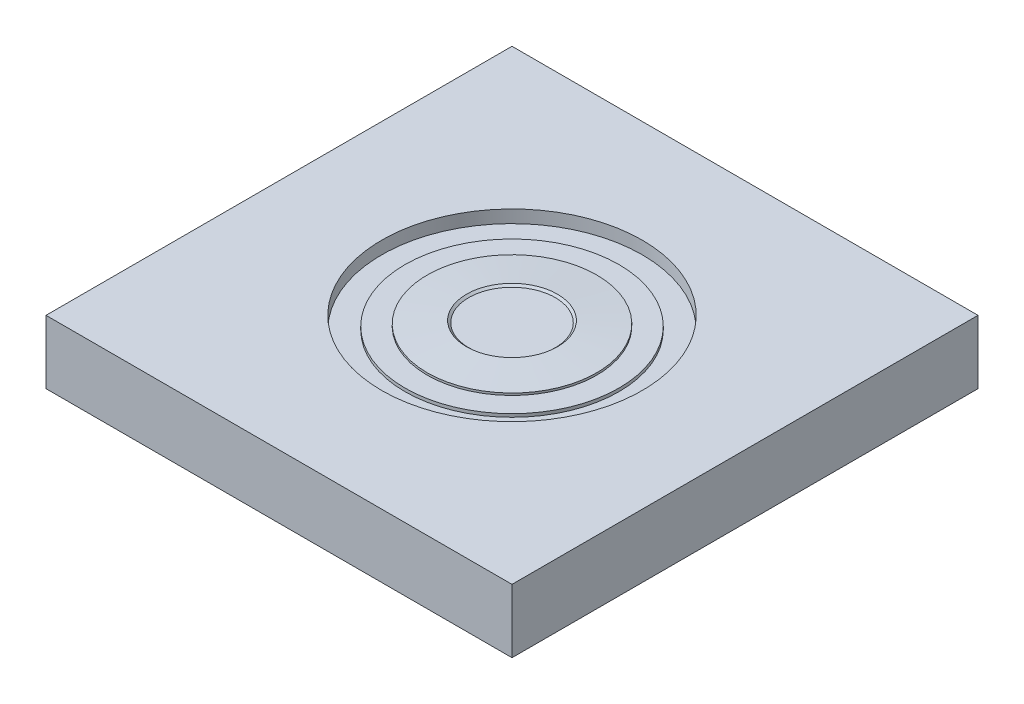
SolidWorks part; units mm, degrees
ref_plane "Front Plane" through (0, 0, 0) normal (0, 0, 1) x (1, 0, 0)
ref_plane "Top Plane" through (0, 0, 0) normal (0, 1, 0) x (1, 0, 0)
ref_plane "Right Plane" through (0, 0, 0) normal (1, 0, 0) x (0, 0, -1)
sketch "Sketch1" plane through (0, 0, 0) normal (0, 1, 0) x (1, 0, 0)
  line L0 (0, 0) -> (0, 237921.0776) construction
  line L1 (0, 0) -> (-237921.0776, 0) construction
  line L3 (110, -110) -> (-110, -110)
  line L4 (110, -110) -> (110, 110)
  line L5 (110, 110) -> (-110, 110)
  line L6 (-110, -110) -> (-110, 110)
  line L7 (110, -110) -> (-110, 110) construction
  line L8 (110, 110) -> (-110, -110) construction
  point P5 (0, 0)
  dimension "D1" = 220
  dimension "D2" = 220
extrude "Boss-Extrude1" add sketch "Sketch1" along normal blind 30
sketch "Sketch2" plane through (0, 30, 0) normal (0, 1, 0) x (1, 0, 0)
  line L0 (0, 0) -> (0, 50000) construction
  line L1 (0, 0) -> (-50000, 0) construction
  circle A0 centre (0, 0) radius 61.5
  circle A1 centre (0, 0) radius 50.5
  dimension "D1" = 123
  dimension "D2" = 101
extrude "Cut-Extrude1" cut sketch "Sketch2" against normal blind 6
sketch "Sketch3" plane through (0, 30, 0) normal (0, 1, 0) x (1, 0, 0)
  circle A0 centre (0, 0) radius 50.5
  circle A1 centre (0, 0) radius 40
  dimension "D1" = 101
  dimension "D2" = 80
extrude "Cut-Extrude2" cut sketch "Sketch3" against normal blind 4.5
sketch "Sketch4" plane through (0, 30, 0) normal (0, 1, 0) x (1, 0, 0)
  circle A0 centre (0, 0) radius 40
  dimension "D1" = 80
extrude "Cut-Extrude3" cut sketch "Sketch4" against normal blind 3.5
sketch "Sketch5" plane through (0, 26.5, 0) normal (0, 1, 0) x (1, 0, 0)
  circle A0 centre (0, 0) radius 40
  dimension "D1" = 80
ref_plane "Plane1" through (0, 28, 0) normal (0, 1, 0) x (1, 0, 0)
sketch "Sketch6" plane through (0, 28, 0) normal (0, 1, 0) x (1, 0, 0)
  circle A0 centre (0, 0) radius 20
  dimension "D1" = 40
loft "Loft1" add profiles "Sketch5", "Sketch6" connector at (7.742, 26.5, 39.2436) connector at (4.2401, 28, 19.5454)
sketch "Sketch8" plane through (0, 28, 0) normal (0, 1, 0) x (1, 0, 0)
  circle A1 centre (0, 0) radius 20
  circle A2 centre (0, 0) radius 20
  dimension "D1" = 0
extrude "Cut-Extrude4" cut sketch "Sketch8" against normal blind 1
chamfer "Chamfer1" distance 1.5 angle 45 1 edges at (0, 28, 20) first distance on face at (0, 26.5, 40)
